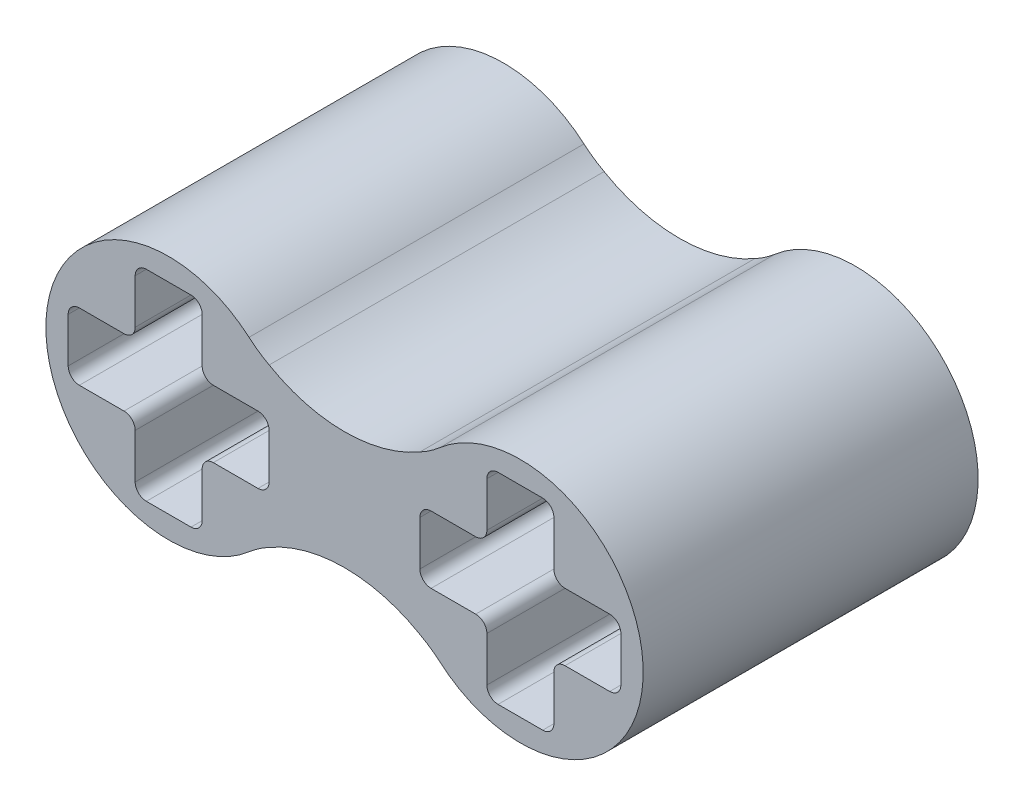
SolidWorks part; units mm, degrees
material "ABS PC"
ref_plane "Front Plane" through (0, 0, 0) normal (0, 0, 1) x (1, 0, 0)
ref_plane "Top Plane" through (0, 0, 0) normal (0, 1, 0) x (1, 0, 0)
ref_plane "Right Plane" through (0, 0, 0) normal (1, 0, 0) x (0, 0, -1)
sketch "Sketch2" plane through (0, 0, 0) normal (0, 0, 1) x (1, 0, 0)
  circle A0 centre (0, 0) radius 2.794
  dimension "D1" = 5.588
extrude "Extrude1" add sketch "Sketch2" along normal blind 7.62
sketch "Sketch3" plane through (0, 0, 7.62) normal (0, 0, 1) x (1, 0, 0)
  line L0 (-0.762, 2.032) -> (-0.762, 1.016)
  line L1 (-1.016, 0.762) -> (-2.032, 0.762)
  line L2 (-2.286, 0.508) -> (-2.286, -0.508)
  line L3 (-2.032, -0.762) -> (-1.016, -0.762)
  line L4 (-0.762, -1.016) -> (-0.762, -2.032)
  line L5 (-0.508, -2.286) -> (0.508, -2.286)
  line L6 (0.762, -2.032) -> (0.762, -1.016)
  line L7 (1.016, -0.762) -> (2.032, -0.762)
  line L8 (2.286, -0.508) -> (2.286, 0.508)
  line L9 (2.032, 0.762) -> (1.016, 0.762)
  line L10 (0.762, 1.016) -> (0.762, 2.032)
  line L11 (0.508, 2.286) -> (-0.508, 2.286)
  line L12 (0, -18.7166) -> (0, 18.7166) construction
  line L13 (35.7523, 0) -> (-35.7523, 0) construction
  arc A0 (-0.762, 1.016) -> (-1.016, 0.762) centre (-1.016, 1.016) cw
  arc A1 (-0.762, 2.032) -> (-0.508, 2.286) centre (-0.508, 2.032) cw
  arc A2 (0.508, 2.286) -> (0.762, 2.032) centre (0.508, 2.032) cw
  arc A3 (0.762, 1.016) -> (1.016, 0.762) centre (1.016, 1.016) ccw
  arc A4 (2.032, 0.762) -> (2.286, 0.508) centre (2.032, 0.508) cw
  arc A5 (2.032, -0.762) -> (2.286, -0.508) centre (2.032, -0.508) ccw
  arc A6 (1.016, -0.762) -> (0.762, -1.016) centre (1.016, -1.016) ccw
  arc A7 (0.762, -2.032) -> (0.508, -2.286) centre (0.508, -2.032) cw
  arc A8 (-0.508, -2.286) -> (-0.762, -2.032) centre (-0.508, -2.032) cw
  arc A9 (-1.016, -0.762) -> (-0.762, -1.016) centre (-1.016, -1.016) cw
  arc A10 (-2.032, -0.762) -> (-2.286, -0.508) centre (-2.032, -0.508) cw
  arc A11 (-2.286, 0.508) -> (-2.032, 0.762) centre (-2.032, 0.508) cw
  point P40 (0, 0)
  dimension "D6" = 0.254
  dimension "D1" = 4.572
  dimension "D2" = 4.572
  dimension "D3" = 1.524
  dimension "D4" = 1.524
  dimension "D5" = 1.524
extrude "Cut-Extrude1" cut sketch "Sketch3" against normal through all
sketch "Sketch4" plane through (0, 0, 7.62) normal (0, 0, 1) x (1, 0, 0)
  line L0 (0, 0) -> (8.001, 0)
  dimension "D1" = 8.001
pattern_linear "LPattern1" count 2 spacing 8.001 along (1, 0, 0) of bodies 102
sketch "Sketch5" plane through (0, 0, 7.62) normal (0, 0, 1) x (1, 0, 0)
  line L1 (0, 0) -> (8.001, 0) construction
  line L2 (2.286, 1.7973) -> (2.286, -1.7973)
  line L3 (5.715, 1.7973) -> (5.715, -1.7973)
  line L4 (5.715, 0.508) -> (5.715, -0.508) construction
  line L5 (2.286, -0.508) -> (2.286, 0.508) construction
  arc A0 (2.286, 1.7973) -> (5.715, 1.7973) centre (4.0005, 4.7684) ccw
  arc A1 (5.715, -1.7973) -> (2.286, -1.7973) centre (4.0005, -4.7684) ccw
  circle A3 centre (8.001, 0) radius 2.794 construction
  circle A4 centre (0, 0) radius 2.794 construction
extrude "Extrude3" add sketch "Sketch5" against normal through all
fillet "Fillet1" radius 2.54 4 edges at (2.286, 1.6064, 3.81) (2.286, -1.6064, 3.81) (5.715, -1.6064, 3.81) (5.715, 1.6064, 3.81)
